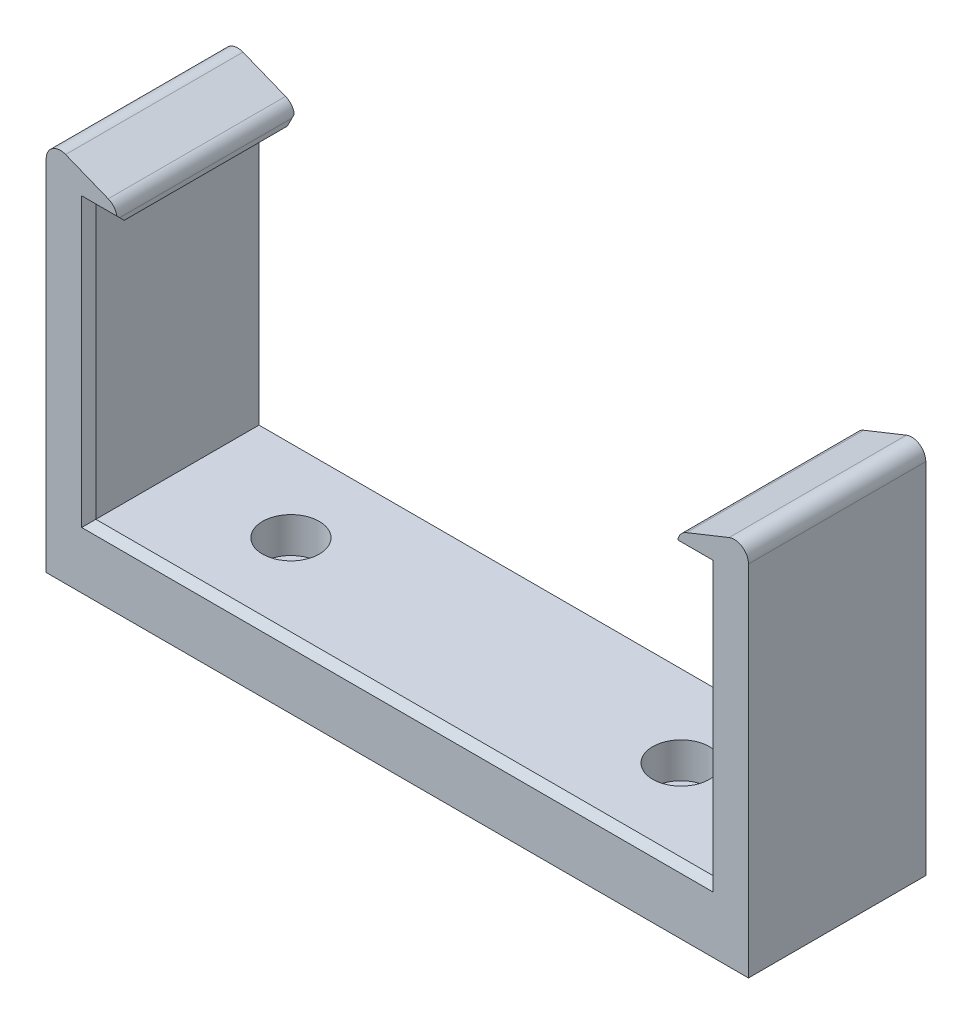
SolidWorks part; units mm, degrees
ref_plane "Front Plane" through (0, 0, 0) normal (0, 0, 1) x (1, 0, 0)
ref_plane "Top Plane" through (0, 0, 0) normal (0, 1, 0) x (1, 0, 0)
ref_plane "Right Plane" through (0, 0, 0) normal (1, 0, 0) x (0, 0, -1)
sketch "Sketch2" plane through (0, 0, 0) normal (0, 0, 1) x (1, 0, 0)
  line L1 (0, 0) -> (87, 0)
  line L3 (0, -10) -> (87, -10)
  line L5 (0, -10) -> (-6, -10)
  line L6 (0, 0) -> (0, 38.5)
  line L8 (-6, -10) -> (-6, 38.5)
  line L13 (0, 38.5) -> (4, 38.5)
  line L14 (-6, 38.5) -> (-6, 44.5)
  line L21 (-6, 44.5) -> (4, 40.5)
  line L22 (4, 40.5) -> (4, 38.5)
  line L23 (43.5, 76.3074) -> (43.5, -37.2767) construction
  line L24 (83, 40.5) -> (83, 38.5)
  line L25 (93, 44.5) -> (83, 40.5)
  line L26 (93, 38.5) -> (93, 44.5)
  line L27 (87, 38.5) -> (83, 38.5)
  line L28 (93, -10) -> (93, 38.5)
  line L29 (87, 0) -> (87, 38.5)
  line L30 (87, -10) -> (93, -10)
  point P9 (43.5, -10)
  point P10 (43.5, 0)
  dimension "D1" = 43.5
  dimension "D2" = 54.5
  dimension "D3" = 10
  dimension "D4" = 6
  dimension "D5" = 38.5
  dimension "D6" = 4
  dimension "D8" = 2
extrude "Boss-Extrude1" add sketch "Sketch2" along normal blind 25
sketch "Sketch3" plane through (0, 0, 0) normal (0, 1, 0) x (1, 0, 0)
  line L0 (43.5, 0) -> (43.5, -25) construction
  line L1 (87, 0) -> (0, 0) construction
  line L2 (87, -25) -> (0, -25) construction
  line L3 (4, -12.5) -> (83, -12.5) construction
  line L4 (4, -25) -> (4, 0) construction
  line L5 (83, -25) -> (83, 0) construction
  circle A0 centre (16, -12.5) radius 4
  circle A1 centre (16, -12.5) radius 2.1
  circle A2 centre (71, -12.5) radius 2.1
  circle A3 centre (71, -12.5) radius 4
  point P15 (0, 0)
  dimension "D1" = 8
  dimension "D2" = 4.2
  dimension "D3" = 12
extrude "Cut-Extrude1" cut sketch "Sketch3" against normal through all contours A1 | A2 region at (16, 0, 12.5) region at (71, 0, 12.5)
extrude "Cut-Extrude2" cut sketch "Sketch3<3>" against normal blind 5 contours A0 A1 | A3 A2 region at (12.1131, 0, 12.5) region at (67.1131, 0, 12.5)
sketch "Sketch3<3>" plane through (0, 0, 0) normal (0, 1, 0) x (1, 0, 0) same geometry as "Sketch3"
fillet "Fillet1" radius 2 4 edges at (-6, 44.5, 12.5) (93, 44.5, 12.5) (83, 40.5, 12.5) (4, 40.5, 12.5)
chamfer "Chamfer1" distance 1 angle 45 14 edges at (2, 38.5, 25) (0, 19.25, 25) (85, 38.5, 25) (87, 19.25, 25) (43.5, 0, 25) (85, 38.5, 0) (87, 19.25, 0) (43.5, 0, 0) (2, 38.5, 0) (0, 19.25, 0) (93, -10, 12.5) (43.5, -10, 0) (-6, -10, 12.5) (43.5, -10, 25)
